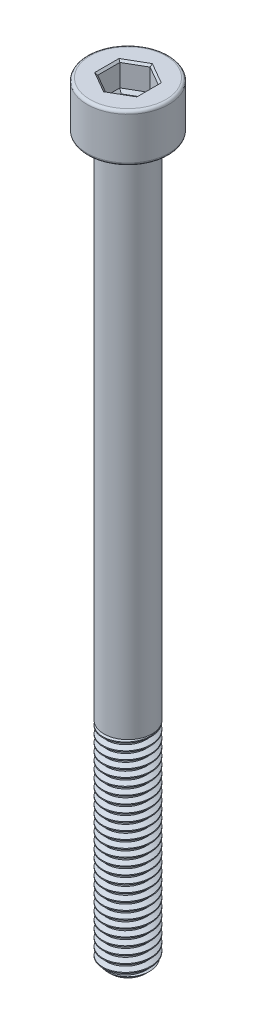
SolidWorks part; units mm, degrees
material "AISI Type A2 Tool Steel"
ref_plane "Front Plane" through (0, 0, 0) normal (0, 0, 1) x (1, 0, 0)
ref_plane "Top Plane" through (0, 0, 0) normal (0, 1, 0) x (1, 0, 0)
ref_plane "Right Plane" through (0, 0, 0) normal (1, 0, 0) x (0, 0, -1)
sketch "Sketch1" plane through (0, 0, 0) normal (0, 1, 0) x (1, 0, 0)
  circle A0 centre (0, 0) radius 2.5
  dimension "D1" = 5
extrude "Boss-Extrude1" add sketch "Sketch1" along normal blind 22
thread "Thread1" pitch 0.8 start angle 0, offset 1, length 0, pitch 0.8, diameter 5
ref_plane "Plane1" through (-2.5, 23, 0) normal (0, 0, 1) x (-1, 0, 0)
sketch "Thread Profile1" plane through (-2.5, 23, 0) normal (0, 0, 1) x (-1, 0, 0)
  line L0 (0, 0) -> (0, 0.8) construction
  line L11 (0, 0) -> (0, 0.7)
  line L12 (0, 0.7) -> (-0.433, 0.45)
  line L13 (-0.433, 0.45) -> (-0.433, 0.25)
  line L15 (-0.433, 0.25) -> (0, 0)
  line L17 (-0.433, 0.35) -> (0, 0.35) construction
  point P2 (0, 0)
  dimension "Pitch" = 0.8
  dimension "Profile_Angle" = 60
  dimension "Profile_Land" = 0.2
  dimension "Profile_Height" = 0.433
sketch "Sketch2" plane through (0, 22, 0) normal (0, 1, 0) x (1, 0, 0)
  circle A0 centre (0, 0) radius 2.5
  dimension "D1" = 5
extrude "Boss-Extrude2" add sketch "Sketch2" along normal blind 53
sketch "Sketch3" plane through (0, 75, 0) normal (0, 1, 0) x (1, 0, 0)
  circle A0 centre (0, 0) radius 4.25
  dimension "D1" = 8.5
extrude "Boss-Extrude3" add sketch "Sketch3" along normal blind 5
fillet "Fillet1" radius 0.3 2 edges at (0, 75, 4.25) (0, 80, 4.25)
sketch "Sketch4" plane through (0, 0, 0) normal (0, 0, 1) x (1, 0, 0)
  line L0 (0, 0) -> (0, 0.4416) construction
  line L1 (0, 0) -> (2.51, 0) construction
  line L2 (2.51, 0) -> (2.51, 0.7)
  line L3 (2.51, 0.7) -> (1.81, 0)
  line L4 (1.81, 0) -> (2.51, 0)
  dimension "D1" = 0.7
  dimension "D2" = 45
  dimension "D3" = 2.51
revolve "Cut-Revolve1" cut sketch "Sketch4" angle 360 about L0
sketch "Sketch5" plane through (0, 80, 0) normal (0, 1, 0) x (1, 0, 0)
  line L1 (0, 2.3094) -> (-2, 1.1547)
  line L2 (-2, 1.1547) -> (-2, -1.1547)
  line L3 (-2, -1.1547) -> (0, -2.3094)
  line L4 (0, -2.3094) -> (2, -1.1547)
  line L5 (2, -1.1547) -> (2, 1.1547)
  line L6 (2, 1.1547) -> (0, 2.3094)
  circle A0 centre (0, 0) radius 2 construction
  dimension "D1" = 4
extrude "Cut-Extrude1" cut sketch "Sketch5" against normal blind 2.5
chamfer "Chamfer1" distance 0.2 angle 45 6 edges at (-1, 80, 1.7321) (1, 80, 1.7321) (2, 80, 0) (1, 80, -1.7321) (-1, 80, -1.7321) (-2, 80, 0)
sketch "Sketch6" plane through (0, 77.5, 0) normal (0, 1, 0) x (1, 0, 0)
  line L1 (0, 2.3094) -> (-2, 1.1547)
  line L2 (-2, 1.1547) -> (-2, -1.1547)
  line L3 (-2, -1.1547) -> (0, -2.3094)
  line L4 (0, -2.3094) -> (2, -1.1547)
  line L5 (2, -1.1547) -> (2, 1.1547)
  line L6 (2, 1.1547) -> (0, 2.3094)
  circle A0 centre (0, 0) radius 2 construction
extrude "Cut-Extrude2" cut sketch "Sketch6" against normal blind 0.3 draft 45
